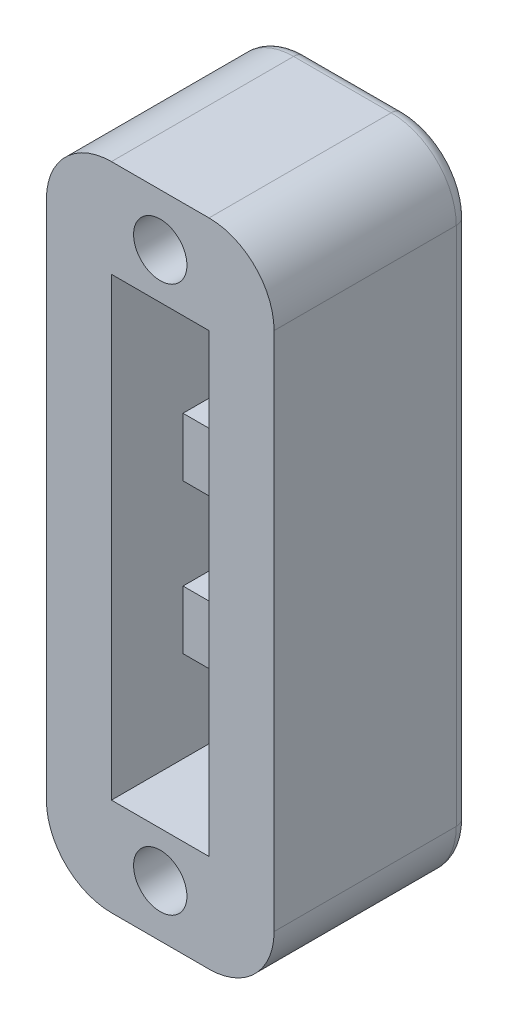
SolidWorks part; units mm, degrees
ref_plane "Front Plane" through (0, 0, 0) normal (0, 0, 1) x (1, 0, 0)
ref_plane "Top Plane" through (0, 0, 0) normal (0, 1, 0) x (1, 0, 0)
ref_plane "Right Plane" through (0, 0, 0) normal (1, 0, 0) x (0, 0, -1)
sketch "Sketch1" plane through (0, 0, 0) normal (0, 1, 0) x (1, 0, 0)
  line L1 (-4.445, -3.81) -> (4.445, -3.81)
  line L2 (-4.445, -3.81) -> (-4.445, 3.81)
  line L3 (-4.445, 3.81) -> (4.445, 3.81)
  line L4 (4.445, -3.81) -> (4.445, 3.81)
  line L5 (-4.445, -3.81) -> (4.445, 3.81) construction
  line L6 (-4.445, 3.81) -> (4.445, -3.81) construction
  point P0 (0, 0)
  dimension "D1" = 8.89
  dimension "D2" = 7.62
extrude "Boss-Extrude1" add sketch "Sketch1" along normal blind 25.4
sketch "Sketch2" plane through (0, 0, 3.81) normal (0, 0, 1) x (1, 0, 0)
  line L0 (-4.445, 25.4) -> (-4.445, 0) construction
  line L1 (-1.905, 3.81) -> (1.905, 3.81)
  line L2 (-1.905, 3.81) -> (-1.905, 21.59)
  line L3 (-1.905, 21.59) -> (1.905, 21.59)
  line L4 (1.905, 3.81) -> (1.905, 21.59)
  line L5 (4.445, 25.4) -> (4.445, 0) construction
  line L6 (-4.445, 25.4) -> (4.445, 25.4) construction
  line L8 (-4.445, 0) -> (4.445, 0) construction
  line L11 (4.445, 0) -> (4.445, 25.4) construction
  dimension "D1" = 2.54
  dimension "D2" = 2.54
  dimension "D4" = 3.81
  dimension "D3" = 3.81
extrude "Cut-Extrude1" cut sketch "Sketch2" against normal offset from surface (5.334 mm away) 2.286 up to face at (0, 12.7, -3.81)
sketch "Sketch3" plane through (1.905, 0, 0) normal (-1, 0, 0) x (0, 0, 1)
  line L0 (-1.524, 21.59) -> (-1.524, 3.81) construction
  line L1 (-1.524, 15.494) -> (1.016, 15.494)
  line L2 (-1.524, 15.494) -> (-1.524, 13.208)
  line L3 (-1.524, 13.208) -> (1.016, 13.208)
  line L4 (1.016, 15.494) -> (1.016, 13.208)
  line L6 (-1.524, 9.652) -> (1.016, 9.652)
  line L7 (-1.524, 9.652) -> (-1.524, 7.366)
  line L8 (-1.524, 7.366) -> (1.016, 7.366)
  line L9 (1.016, 9.652) -> (1.016, 7.366)
  line L10 (-1.524, 19.05) -> (1.016, 19.05)
  line L11 (-1.524, 19.05) -> (-1.524, 21.59)
  line L12 (-1.524, 21.59) -> (1.016, 21.59)
  line L13 (1.016, 19.05) -> (1.016, 21.59)
  line L15 (-1.524, 3.81) -> (3.81, 3.81) construction
  point P14 (-0.254, 9.652)
  dimension "D1" = 3.556
  dimension "D2" = 3.556
  dimension "D3" = 2.54
  dimension "D4" = 2.286
  dimension "D5" = 2.286
  dimension "D6" = 2.54
  dimension "D7" = 2.54
  dimension "D8" = 2.54
  dimension "D9" = 3.556
extrude "Boss-Extrude2" add sketch "Sketch3" along normal up to surface (3.81 mm away) up to face at (-1.905, 12.7, 1.143)
sketch "Sketch4" plane through (0, 0, -1.524) normal (0, 0, 1) x (1, 0, 0)
  line L1 (-1.905, 7.366) -> (1.905, 7.366)
  line L2 (-1.905, 7.366) -> (-1.905, 3.81)
  line L3 (-1.905, 3.81) -> (1.905, 3.81)
  line L4 (1.905, 7.366) -> (1.905, 3.81)
extrude "Cut-Extrude2" cut sketch "Sketch4" against normal through all
sketch "Sketch5" plane through (0, 0, 3.81) normal (0, 0, 1) x (1, 0, 0)
  line L0 (-4.445, 25.4) -> (4.445, 25.4) construction
  circle A1 centre (0, 2.032) radius 1.0414
  circle A2 centre (0, 23.368) radius 1.0414
  dimension "D1" = 2.032
  dimension "D2" = 2.032
extrude "Cut-Extrude4" cut sketch "Sketch5" against normal through all
fillet "Fillet3" radius 2.54 4 edges at (-4.445, 0, 0) (4.445, 0, 0) (4.445, 25.4, 0) (-4.445, 25.4, 0)
fillet "Fillet2" radius 0.508 8 edges at (4.445, 12.7, -3.81) (0, 0, -3.81) (-4.445, 12.7, -3.81) (0, 25.4, -3.81) (3.7011, 24.6561, -3.81) (3.7011, 0.7439, -3.81) (-3.7011, 0.7439, -3.81) (-3.7011, 24.6561, -3.81)
equation "\"D2@Sketch2\"=\"D1@Sketch2\""
equation "\"D2@Sketch3\"=\"D1@Sketch3\""
equation "\"D5@Sketch3\"=\"D4@Sketch3\""
equation "\"D7@Sketch3\"=\"D6@Sketch3\""
equation "\"D8@Sketch3\"=\"D6@Sketch3\""
equation "\"D3@Sketch2\"=\"D4@Sketch2\""
equation "\"D2@Sketch5\"=\"D1@Sketch5\""
